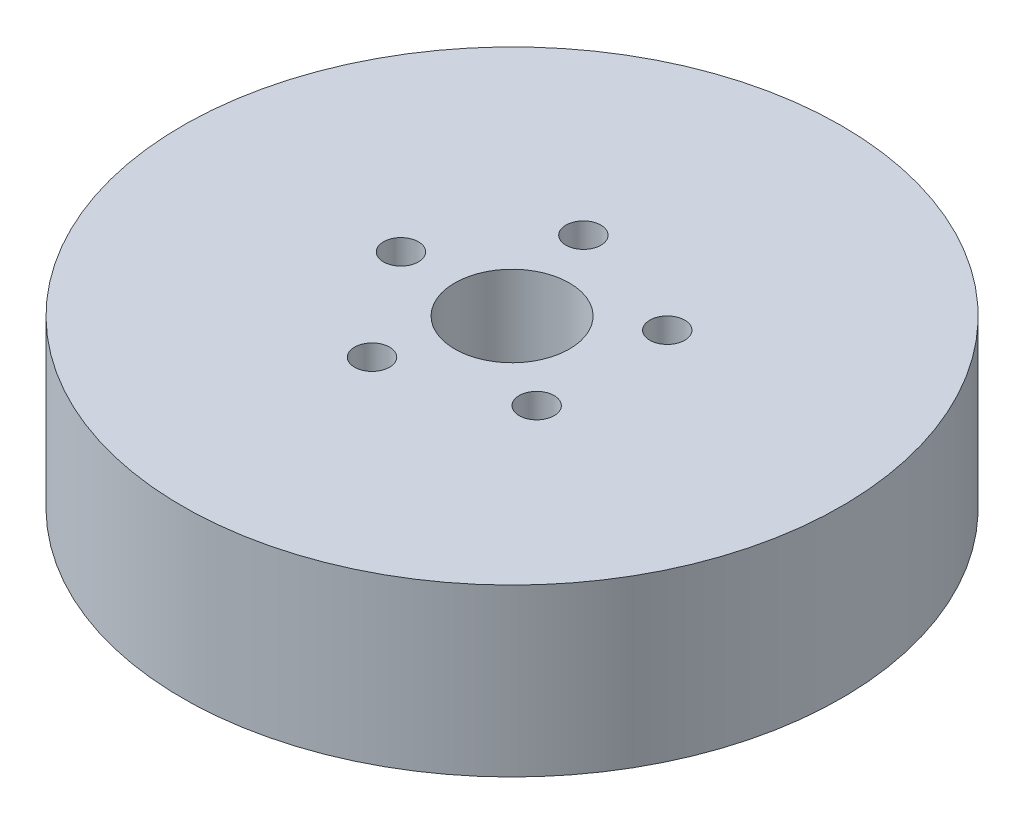
SolidWorks part; units mm, degrees
ref_plane "Front Plane" through (0, 0, 0) normal (0, 0, 1) x (1, 0, 0)
ref_plane "Top Plane" through (0, 0, 0) normal (0, 1, 0) x (1, 0, 0)
ref_plane "Right Plane" through (0, 0, 0) normal (1, 0, 0) x (0, 0, -1)
sketch "Sketch1" plane through (0, 0, 0) normal (0, 1, 0) x (1, 0, 0)
  circle A0 centre (0, 0) radius 57.5
  dimension "FLANGE_OD" = 115
extrude "Boss-Extrude1" add sketch "Sketch1" along normal blind 29
sketch "Sketch2" plane through (0, 0, 0) normal (0, 1, 0) x (1, 0, 0)
  circle A0 centre (0, 0) radius 10
  dimension "BORE_D" = 20
extrude "Cut-Extrude1" cut sketch "Sketch2" along normal through all
sketch "Sketch3" plane through (0, 29, 0) normal (0, 1, 0) x (1, 0, 0)
  circle A0 centre (0, 0) radius 19.3868 construction
  circle A1 centre (-19.3868, 0) radius 3.0501
  dimension "BOLT_D" = 6.1001
  dimension "BOLT_PCD" = 38.7737
extrude "Cut-Extrude2" cut sketch "Sketch3" against normal blind 18.8127
pattern_circular "CirPattern1" count 5 over 360 about axis through (0, 0, 0) along (0, 1, 0) of "Cut-Extrude2"
